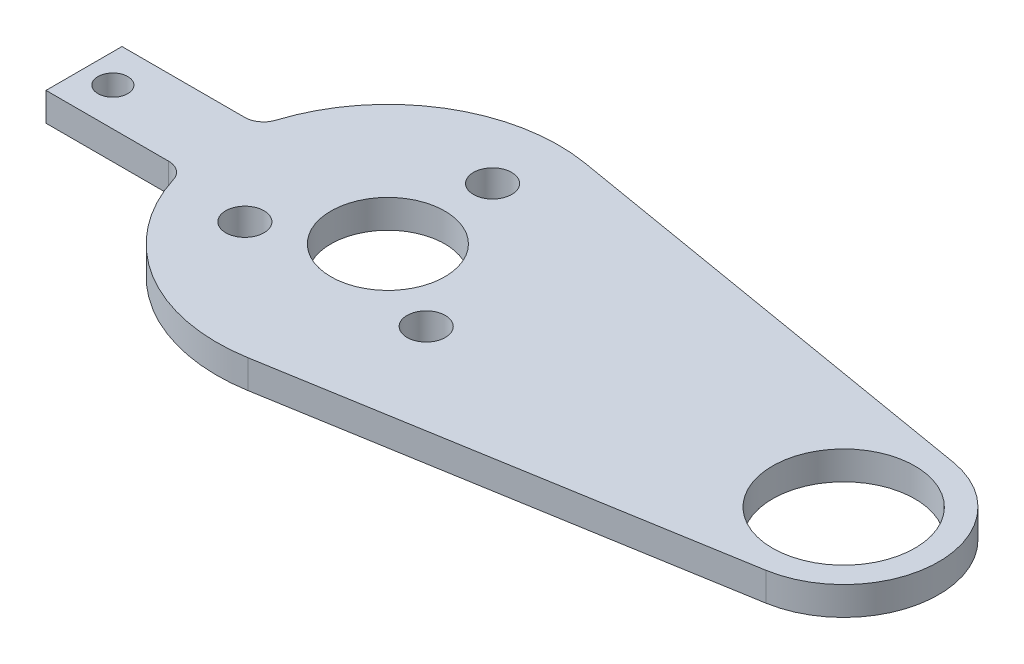
SolidWorks part; units mm, degrees
material "Alloy Steel"
ref_plane "Front Plane" through (0, 0, 0) normal (0, 0, 1) x (1, 0, 0)
ref_plane "Top Plane" through (0, 0, 0) normal (0, 1, 0) x (1, 0, 0)
ref_plane "Right Plane" through (0, 0, 0) normal (1, 0, 0) x (0, 0, -1)
sketch "Sketch1" plane through (0, 0, 0) normal (0, 1, 0) x (1, 0, 0)
  line L0 (0, 0) -> (76.2, 0) construction
  line L1 (4.7625, 28.1753) -> (78.8458, 15.653)
  line L2 (4.7625, -28.1753) -> (78.8458, -15.653)
  line L3 (0, 0) -> (-50.8, 0) construction
  line L5 (-27.8605, -6.35) -> (-50.8, -6.35)
  line L7 (-27.8605, 6.35) -> (-50.8, 6.35)
  line L8 (-50.8, -6.35) -> (-50.8, 6.35)
  line L9 (-28.575, 0) -> (-50.8, 6.35) construction
  line L10 (-28.575, 0) -> (-50.8, -6.35) construction
  arc A0 (4.7625, 28.1753) -> (-27.8605, 6.35) centre (0, 0) ccw
  arc A1 (78.8458, -15.653) -> (78.8458, 15.653) centre (76.2, 0) ccw
  arc A2 (-27.8605, -6.35) -> (4.7625, -28.1753) centre (0, 0) ccw
  point P6 (-28.575, 0)
  dimension "D1" = 57.15
  dimension "D2" = 31.75
  dimension "D3" = 76.2
  dimension "D4" = 12.7
  dimension "D5" = 50.8
extrude "Boss-Extrude1" add sketch "Sketch1" along normal blind 4.7625
sketch "Sketch2" plane through (0, 4.7625, 0) normal (0, 1, 0) x (1, 0, 0)
  circle A0 centre (76.2, 0) radius 11.9062
  dimension "D1" = 23.8125
extrude "Cut-Extrude1" cut sketch "Sketch2" against normal through all
sketch "Sketch3" plane through (0, 4.7625, 0) normal (0, 1, 0) x (1, 0, 0)
  circle A0 centre (0, 0) radius 17.5 construction
  point P3 (0, 17.5)
  point P4 (15.1554, -8.75)
  point P7 (-15.1554, -8.75)
  point P8 (0, 0)
  dimension "D1" = 35
  dimension "D2" = 3
hole_wizard "M6 Clearance Hole1" positions "3DSketch1" profile "Sketch4" hole size "M6" standard "ANSI Metric" end condition through all
sketch3d "3DSketch1"
  point P0 (0, 4.7625, -17.5)
  point P3 (-15.1554, 4.7625, 8.75)
  point P6 (15.1554, 4.7625, 8.75)
sketch "Sketch4" plane through (0, 4.7625, -17.5) normal (1, 0, 0) x (0, 0, 1)
  line L0 (0, 0) -> (0, 4.7625)
  line L1 (0, 4.7625) -> (3.2, 4.7625)
  line L2 (3.2, 4.7625) -> (3.2, 0)
  line L5 (3.2, 0) -> (0, 0)
  line L11 (0, -6.35) -> (0, 107.95) construction
  dimension "Thru Hole Dia." = 6.4
  dimension "Thru Hole Depth" = 4.7625
sketch "Sketch5" plane through (0, 4.7625, 0) normal (0, 1, 0) x (1, 0, 0)
  circle A0 centre (0, 0) radius 9.525
  dimension "D1" = 19.05
extrude "Cut-Extrude2" cut sketch "Sketch5" against normal through all
fillet "Fillet1" radius 3.175 2 edges at (-27.8605, 2.3813, 6.35) (-27.8605, 2.3813, -6.35)
sketch "Sketch6" plane through (0, 4.7625, 0) normal (0, 1, 0) x (1, 0, 0)
  line L0 (-50.8, 0) -> (-9.525, 0) construction
  line L1 (-50.8, 6.35) -> (-50.8, -6.35) construction
  circle A0 centre (0, 0) radius 9.525 construction
  circle A1 centre (-45.974, 0) radius 4.7625 construction
  dimension "D1" = 9.525
  dimension "D2" = 4.826
hole_wizard "#10 Clearance Hole1" positions "3DSketch2" profile "Sketch7" hole size "#10" standard "ANSI Inch"
sketch3d "3DSketch2"
  point P0 (-45.974, 4.7625, 0)
sketch "Sketch7" plane through (-45.974, 4.7625, 0) normal (1, 0, 0) x (0, 0, 1)
  line L0 (0, 0) -> (0, 11.0207)
  line L1 (0, 11.0207) -> (2.4892, 9.525)
  line L2 (2.4892, 9.525) -> (2.4892, 0)
  line L5 (2.4892, 0) -> (0, 0)
  line L10 (0, 11.0207) -> (-2.4892, 9.525) construction
  line L11 (0, -6.35) -> (0, 107.95) construction
  dimension "Hole Dia." = 4.9784
  dimension "Hole Depth" = 9.525
  dimension "Drill Angle" = 118
